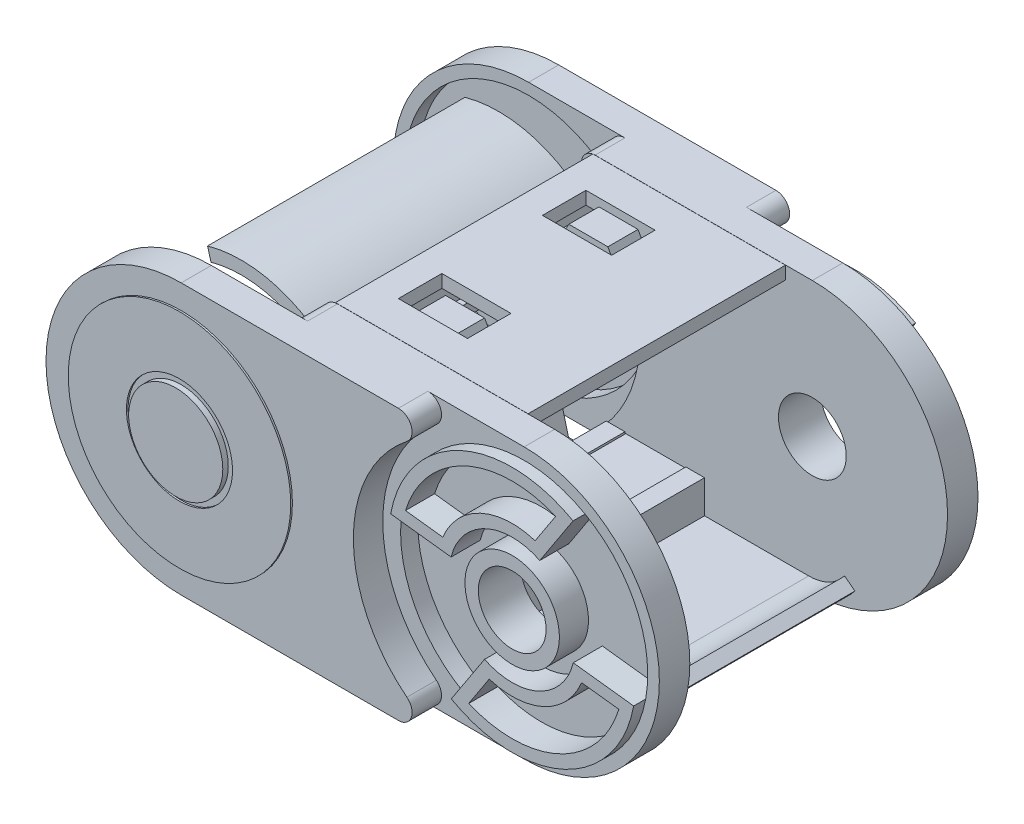
SolidWorks part; units mm, degrees
material "ABS"
ref_plane "Front Plane" through (0, 0, 0) normal (0, 0, 1) x (1, 0, 0)
ref_plane "Top Plane" through (0, 0, 0) normal (0, 1, 0) x (1, 0, 0)
ref_plane "Right Plane" through (0, 0, 0) normal (1, 0, 0) x (0, 0, -1)
sketch "Sketch1" plane through (0, 0, 0) normal (0, 0, 1) x (1, 0, 0)
  line L0 (0, 19.75) -> (45.8, 19.75)
  line L2 (45.8, -19.75) -> (0, -19.75)
  line L3 (0, 0) -> (45.8, 0) construction
  line L4 (22.9, 0) -> (22.9, 19.75) construction
  arc A0 (0, 19.75) -> (0, -19.75) centre (0, 0) ccw
  arc A1 (45.8, 19.75) -> (45.8, -19.75) centre (45.8, 0) cw
  point P1 (-19.75, 0)
  point P12 (65.55, 0)
  dimension "D1" = 39.5
  dimension "D2" = 85.3
  dimension "D3" = 45.8
extrude "Boss-Extrude1" add sketch "Sketch1" against normal blind 8.75 from offset 27.575
sketch "Sketch3" plane through (0, 0, 27.575) normal (0, 0, 1) x (1, 0, 0)
  line L6 (65.55, 0) -> (25.15, 0) construction
  circle A2 centre (45.8, 0) radius 20.65
  circle A3 centre (0, 0) radius 16.25
  arc A4 (45.8, -19.75) -> (45.8, 19.75) centre (45.8, 0) ccw construction
  circle A5 centre (0, 0) radius 7.75
  circle A6 centre (0, 0) radius 5.15
  point P4 (65.55, 0)
  dimension "D1" = 40.4
  dimension "D2" = 10.3
  dimension "D3" = 15.5
  dimension "D4" = 32.5
extrude "Cut-Extrude2" cut sketch "Sketch3" against normal blind 4.3 contours A2
extrude "Cut-Extrude10" cut sketch "Sketch3<3>" against normal through all contours A6 region at (0, 0, 27.575)
sketch "Sketch3<3>" plane through (0, 0, 27.575) normal (0, 0, 1) x (1, 0, 0) same geometry as "Sketch3"
extrude "Boss-Extrude11" add sketch "Sketch3<4>" along normal blind 0.25 contours A3 A5 region at (-15.7904, 0, 27.575)
sketch "Sketch3<4>" plane through (0, 0, 27.575) normal (0, 0, 1) x (1, 0, 0) same geometry as "Sketch3"
sketch "Sketch8" plane through (0, 0, 18.825) normal (0, 0, -1) x (-1, 0, 0)
  line L0 (19.75, 0) -> (-20.65, 0) construction
  circle A0 centre (0, 0) radius 20.65
  arc A1 (0, -19.75) -> (0, 19.75) centre (0, 0) ccw construction
  point P3 (-20.65, 0)
  point P4 (19.75, 0)
  dimension "D1" = 40.4
extrude "Cut-Extrude6" cut sketch "Sketch8" against normal blind 4.35
sketch "Sketch9" plane through (0, 0, 23.175) normal (0, 0, -1) x (-1, 0, 0)
  circle A0 centre (0, 0) radius 18.1
  dimension "D1" = 36.2
extrude "Cut-Extrude7" cut sketch "Sketch9" against normal blind 6.5 from surface starting at face at (34.5075, 0, 18.825)
sketch "Sketch10" plane through (0, 0, 25.325) normal (0, 0, -1) x (-1, 0, 0)
  line L0 (0, 0) -> (16.75, 0) construction
  line L1 (8.5625, 2.5) -> (16.75, 3.2)
  line L2 (16.75, 3.2) -> (16.75, -3.2)
  line L3 (16.75, -3.2) -> (8.5625, -2.5)
  line L4 (8.8724, 0.9207) -> (15.15, 1.4574)
  line L5 (15.15, 1.4574) -> (15.15, -1.4574)
  line L6 (15.15, -1.4574) -> (8.8724, -0.9207)
  line L7 (8.6988, 0.9058) -> (15.15, 1.4574) construction
  line L8 (15.15, -1.4574) -> (8.6988, -0.9058) construction
  line L9 (0, 0) -> (0, -8.92) construction
  line L10 (-8.8724, 0.9207) -> (-15.15, 1.4574)
  line L11 (-15.15, 1.4574) -> (-15.15, -1.4574)
  line L12 (-15.15, -1.4574) -> (-8.8724, -0.9207)
  line L13 (-16.75, -3.2) -> (-8.5625, -2.5)
  line L14 (-16.75, 3.2) -> (-16.75, -3.2)
  line L15 (-8.5625, 2.5) -> (-16.75, 3.2)
  circle A0 centre (0, 0) radius 7
  arc A1 (-8.8724, 0.9207) -> (-8.8724, -0.9207) centre (0, 0) ccw
  arc A2 (-8.5625, -2.5) -> (8.5625, -2.5) centre (0, 0) ccw
  arc A3 (8.5625, 2.5) -> (-8.5625, 2.5) centre (0, 0) ccw
  arc A4 (8.8724, -0.9207) -> (8.8724, 0.9207) centre (0, 0) ccw
  point P7 (16.75, 0)
  dimension "D1" = 14
  dimension "D2" = 17.84
  dimension "D3" = 5
  dimension "D4" = 6.4
  dimension "D5" = 16.75
  dimension "D6" = 1.6
extrude "Boss-Extrude3" add sketch "Sketch10" along normal blind 3.9
fillet "Fillet1" radius 0.5 4 edges at (-16.75, -3.2, 23.375) (-16.75, 3.2, 23.375) (16.75, -3.2, 23.375) (16.75, 3.2, 23.375)
sketch "Sketch11" plane through (0, 0, 21.425) normal (0, 0, -1) x (-1, 0, 0)
  circle A0 centre (0, 0) radius 7 construction
  circle A1 centre (0, 0) radius 7
extrude "Cut-Extrude8" cut sketch "Sketch11" against normal blind 4.6
fillet "Fillet2" radius 2 4 edges at (6.0299, 19.75, 21) (6.0299, -19.75, 21) (39.7701, -19.75, 25.425) (39.7701, 19.75, 25.425)
sketch "Sketch20" plane through (0, 0, 23.275) normal (0, 0, 1) x (1, 0, 0)
  circle A1 centre (45.8, 0) radius 18.05
  circle A2 centre (45.8, 0) radius 4.95
  dimension "D1" = 36.1
  dimension "D2" = 9.9
extrude "Cut-Extrude11" cut sketch "Sketch20" against normal through all contours A2 region at (45.8, 0, 23.275)
extrude "Cut-Extrude12" cut sketch "Sketch20<3>" against normal offset from surface (2.5 mm away) 6.8 contours A1 up to face at (16.25, 0, 27.575)
sketch "Sketch20<3>" plane through (0, 0, 23.275) normal (0, 0, 1) x (1, 0, 0) same geometry as "Sketch20"
sketch "Sketch21" plane through (0, 0, 20.775) normal (0, 0, 1) x (1, 0, 0)
  line L0 (54.6961, 15.7055) -> (49.8334, 8.2687)
  line L1 (45.8, 0) -> (38.1717, 16.3589) construction
  line L2 (28.0506, 3.2805) -> (36.8732, 2.2253)
  line L3 (45.8, 0) -> (63.6996, 8.3467) construction
  line L4 (45.8, 0) -> (0, 0) construction
  line L5 (52.1515, 15.0116) -> (49.152, 10.4243)
  line L6 (30.2178, 4.7838) -> (35.6599, 4.1329)
  line L7 (36.9039, -15.7055) -> (41.7666, -8.2687)
  line L8 (39.4485, -15.0116) -> (42.448, -10.4243)
  line L9 (61.3822, -4.7838) -> (55.9401, -4.1329)
  line L10 (63.5494, -3.2805) -> (54.7268, -2.2253)
  circle A0 centre (45.8, 0) radius 4.95 construction
  circle A1 centre (45.8, 0) radius 4.95
  circle A2 centre (45.8, 0) radius 6.9
  arc A3 (49.8334, 8.2687) -> (36.8732, 2.2253) centre (45.8, 0) ccw
  circle A4 centre (45.8, 0) radius 18.05 construction
  arc A5 (54.6961, 15.7055) -> (28.0506, 3.2805) centre (45.8, 0) ccw
  arc A6 (45.8, -19.75) -> (45.8, 19.75) centre (45.8, 0) ccw construction
  arc A7 (0, 19.75) -> (0, -19.75) centre (0, 0) ccw construction
  arc A8 (49.152, 10.4243) -> (35.6599, 4.1329) centre (45.8, 0) ccw
  arc A9 (52.1515, 15.0116) -> (30.2178, 4.7838) centre (45.8, 0) ccw
  arc A10 (54.7268, -2.2253) -> (41.7666, -8.2687) centre (45.8, 0) cw
  arc A11 (55.9401, -4.1329) -> (42.448, -10.4243) centre (45.8, 0) cw
  arc A12 (61.3822, -4.7838) -> (39.4485, -15.0116) centre (45.8, 0) cw
  arc A13 (63.5494, -3.2805) -> (36.9039, -15.7055) centre (45.8, 0) cw
  point P19 (-19.75, 0)
  dimension "D1" = 13.8
  dimension "D2" = 29.4
  dimension "D4" = 18.4
  dimension "D3" = 14.3
  dimension "D5" = 25
  dimension "D6" = 1.75
extrude "Boss-Extrude12" add sketch "Sketch21" along normal blind 4.25
sketch "Sketch12" plane through (0, 0, 18.825) normal (0, 0, -1) x (-1, 0, 0)
  line L0 (-27.45, 17.15) -> (-18.35, 17.15)
  line L1 (-22.9, 17.15) -> (-22.9, 13.25) construction
  line L2 (-27.45, 17.15) -> (-28.275, 15.65)
  line L3 (-28.275, 14.85) -> (-27.25, 14.85)
  line L4 (-27.25, 14.85) -> (-27.25, 13.25)
  line L5 (-18.55, 14.85) -> (-18.55, 13.25)
  line L6 (-17.525, 14.85) -> (-18.55, 14.85)
  line L7 (-18.35, 17.15) -> (-17.525, 15.65)
  line L8 (-18.55, 13.25) -> (-27.25, 13.25)
  line L9 (-28.275, 15.65) -> (-28.275, 14.85)
  line L10 (0, 0) -> (-45.8, 0) construction
  line L20 (-17.525, 15.65) -> (-17.525, 14.85)
  line L21 (-22.9, -17.15) -> (-22.9, -13.25) construction
  line L22 (-17.525, -15.65) -> (-17.525, -14.85)
  line L23 (-28.275, -15.65) -> (-28.275, -14.85)
  line L24 (-18.55, -13.25) -> (-27.25, -13.25)
  line L25 (-18.35, -17.15) -> (-17.525, -15.65)
  line L26 (-17.525, -14.85) -> (-18.55, -14.85)
  line L27 (-18.55, -14.85) -> (-18.55, -13.25)
  line L28 (-27.25, -14.85) -> (-27.25, -13.25)
  line L29 (-28.275, -14.85) -> (-27.25, -14.85)
  line L30 (-27.45, -17.15) -> (-28.275, -15.65)
  line L31 (-27.45, -17.15) -> (-18.35, -17.15)
  point P3 (-22.9, 17.15)
  point P17 (-22.9, 0)
  dimension "D1" = 10.75
  dimension "D3" = 26.5
  dimension "D4" = 34.3
  dimension "D5" = 8.7
  dimension "D6" = 2.3
  dimension "D7" = 0.8
  dimension "D8" = 9.1
extrude "Boss-Extrude4" add sketch "Sketch12" along normal blind 10.92
sketch "Sketch13" plane through (0, 0, 7.905) normal (0, 0, -1) x (-1, 0, 0)
  line L0 (-26.725, 17.15) -> (-25.75, 18.9)
  line L1 (-18.35, 17.15) -> (-27.45, 17.15) construction
  line L2 (-25.75, 18.9) -> (-20.05, 18.9)
  line L3 (-20.05, 18.9) -> (-19.075, 17.15)
  line L4 (-26.725, 17.15) -> (-19.075, 17.15)
  line L5 (-22.9, 18.9) -> (-22.9, 17.15) construction
  line L6 (0, 0) -> (-45.8, 0) construction
  line L8 (-20.05, -18.9) -> (-19.075, -17.15)
  line L9 (-26.725, -17.15) -> (-19.075, -17.15)
  line L10 (-26.725, -17.15) -> (-25.75, -18.9)
  line L11 (-25.75, -18.9) -> (-20.05, -18.9)
  point P8 (-22.9, 17.15)
  dimension "D1" = 7.65
  dimension "D2" = 5.7
  dimension "D3" = 1.75
extrude "Boss-Extrude5" add sketch "Sketch13" against normal blind 4.4 from offset 1.1 offset against normal yes
sketch "Sketch14" plane through (0, 0, 0) normal (0, 0, 1) x (1, 0, 0)
  line L0 (45.2873, 19.75) -> (8.74, 19.75)
  line L1 (45.8, 19.75) -> (14.0698, 19.75) construction
  line L2 (8.74, 19.75) -> (7.2253, 13.8823)
  line L3 (52.05, 16.3994) -> (50.5543, 15.2605)
  line L4 (45.2873, 17.87) -> (30.075, 17.87)
  line L5 (10.1963, 17.87) -> (8.4, 10.9111)
  line L6 (-10.34, 11.7476) -> (-9.0979, 10.3364)
  line L8 (30.075, 13.05) -> (30.075, 17.87)
  line L9 (27.35, 13.05) -> (30.075, 13.05)
  line L10 (27.35, 13.05) -> (27.35, 14.75)
  line L11 (27.35, 14.75) -> (28.375, 14.75)
  line L12 (28.375, 14.75) -> (28.375, 17.87)
  line L13 (28.375, 17.87) -> (17.425, 17.87)
  line L14 (41.15, 17.87) -> (10.1963, 17.87) construction
  line L15 (18.45, 13.05) -> (15.725, 13.05)
  line L16 (15.725, 13.05) -> (15.725, 17.87)
  line L17 (22.9, 13.25) -> (22.9, 19.75) construction
  line L18 (18.45, 13.25) -> (18.45, 14.75)
  line L19 (17.425, 14.75) -> (17.425, 15.65)
  line L20 (18.45, 14.75) -> (17.425, 14.75)
  line L21 (18.45, 13.05) -> (18.45, 14.75)
  line L22 (17.425, 14.75) -> (17.425, 17.87)
  line L23 (18.45, 14.75) -> (17.425, 14.75)
  line L24 (18.55, 13.25) -> (27.25, 13.25) construction
  line L25 (15.725, 17.87) -> (10.1963, 17.87)
  line L26 (52.05, 16.3994) -> (52.8335, 18.4552) construction
  line L27 (41.15, 19.75) -> (8.74, 19.75) construction
  arc A0 (7.2253, 13.8823) -> (-10.34, 11.7476) centre (0, 0) ccw
  arc A1 (8.4, 10.9111) -> (-9.0979, 10.3364) centre (0, 0) ccw
  arc A3 (45.8, -19.75) -> (45.8, 19.75) centre (45.8, 0) ccw construction
  arc A4 (52.05, 16.3994) -> (45.2873, 19.75) centre (45.2873, 11.25) ccw
  arc A5 (50.5543, 15.2605) -> (45.2873, 17.87) centre (45.2873, 11.25) ccw
  point P28 (65.55, 0)
  point P30 (45.8, 0)
  point P37 (52.05, 16.3994)
  dimension "D1" = 15.65
  dimension "D5" = 2.2
  dimension "D10" = 17
  dimension "D2" = 14.16
  dimension "D3" = 33.24
  dimension "D4" = 14.5
  dimension "D7" = 0.1
  dimension "D9" = 13.5
  dimension "D6" = 1.88
  dimension "D8" = 1.7
extrude "Boss-Extrude6" add sketch "Sketch14" along normal mid plane 37.6 separate body
sketch "Sketch15" plane through (0, 19.75, 0) normal (0, 1, 0) x (1, 0, 0)
  line L1 (27.95, -7.35) -> (17.85, -7.35)
  line L2 (27.95, -7.35) -> (27.95, -13.7)
  line L5 (27.95, -13.7) -> (17.85, -13.7)
  line L6 (17.85, -7.35) -> (17.85, -13.7)
  line L7 (22.9, -13.7) -> (22.9, -7.35) construction
  line L8 (27.95, -10.525) -> (17.85, -10.525) construction
  line L9 (0, 0) -> (44.1536, 0) construction
  line L10 (17.85, 7.35) -> (17.85, 13.7)
  line L11 (27.95, 13.7) -> (17.85, 13.7)
  line L12 (27.95, 7.35) -> (27.95, 13.7)
  line L13 (27.95, 7.35) -> (17.85, 7.35)
  line L14 (19.075, -9.005) -> (26.725, -13.405) construction
  point P14 (22.9, -11.205)
  point P172 (22.9, -10.525)
  dimension "D1" = 10.1
  dimension "D2" = 14.7
  dimension "D3" = 27.4
extrude "Cut-Extrude9" cut sketch "Sketch15" against normal up to surface (5 mm away) up to face at (27.8625, 14.75, 0)
sketch "Sketch16" plane through (0, 13.05, 0) normal (0, -1, 0) x (1, 0, 0)
  line L5 (30.075, 0) -> (15.725, 0) construction
  line L6 (30.075, 18.8) -> (30.075, -18.8) construction
  line L13 (15.725, 18.8) -> (15.725, -18.8) construction
  line L14 (30.075, 1) -> (15.725, 1)
  line L15 (30.075, -1) -> (15.725, -1)
  line L16 (30.075, 1) -> (30.075, -1)
  line L17 (15.725, 1) -> (15.725, -1)
  dimension "D1" = 1
  dimension "D2" = 1
extrude "Boss-Extrude7" add sketch "Sketch16" against normal up to surface (4.82 mm away) up to face at (37.6812, 17.87, 0)
sketch "Sketch18" plane through (0, 0, 27.575) normal (0, 0, 1) x (1, 0, 0)
  circle A0 centre (0, 0) radius 6.875
  dimension "D1" = 13.75
extrude "Boss-Extrude9" add sketch "Sketch18" along normal blind 0.8 separate body
sketch "Sketch19" plane through (0, 0, 27.575) normal (0, 0, -1) x (-1, 0, 0)
  circle A2 centre (0, 0) radius 5.1
  circle A4 centre (0, 0) radius 5.1
  dimension "D1" = 0.05
extrude "Boss-Extrude10" add sketch "Sketch19" along normal blind 8
mirror "Mirror1" about plane through (0, 0, 0) normal (0, 0, 1) of bodies 113 121
mirror "Mirror2" about plane through (0, 0, 0) normal (0, 1, 0) of bodies 118 115
sketch "Sketch22" plane through (0, -19.75, 0) normal (0, -1, 0) x (1, 0, 0)
  line L0 (45.8, 18.825) -> (65.55, 18.825) construction
  line L1 (54.05, 18.825) -> (41.9, 18.825)
  line L2 (54.05, 18.825) -> (54.05, -18.825)
  line L3 (54.05, -18.825) -> (41.9, -18.825)
  line L4 (41.9, 18.825) -> (41.9, -18.825)
  line L5 (47.975, -18.825) -> (47.975, 18.825) construction
  line L6 (54.05, 0) -> (41.9, 0) construction
  line L7 (14.0698, -18.825) -> (45.8, -18.825) construction
  line L8 (52.05, 18.8) -> (52.05, -18.8) construction
  line L9 (25.75, 13.405) -> (20.05, 13.405) construction
  point P14 (22.9, 13.405)
  point P268 (47.975, 0)
  dimension "D1" = 2
  dimension "D2" = 19
extrude "Cut-Extrude13" cut sketch "Sketch22" against normal through all
sketch "Sketch23" plane through (0, 0, 0) normal (0, 0, 1) x (1, 0, 0)
  line L0 (15.225, 17.87) -> (14.1999, 13.8987)
  line L1 (8.4, 10.9111) -> (10.1963, 17.87) construction
  line L2 (10.1963, 17.87) -> (15.725, 17.87) construction
  line L3 (15.225, 17.87) -> (15.225, 19.75)
  line L4 (41.9, 19.75) -> (8.74, 19.75) construction
  line L5 (15.225, 19.75) -> (13.7687, 19.75)
  line L6 (13.7687, 19.75) -> (12.3795, 14.3685)
  line L7 (10.1963, 17.87) -> (8.376, 18.3399) construction
  line L8 (8.74, 19.75) -> (7.2253, 13.8823) construction
  line L9 (14.7124, 15.8843) -> (12.8921, 16.3542) construction
  line L10 (-4.925, 17.5729) -> (-4.4177, 15.7627)
  line L11 (30.075, 13.05) -> (30.075, 17.87) construction
  arc A1 (10.3855, 12.6538) -> (-4.4177, 15.7627) centre (0, 0) ccw
  arc A3 (11.5782, 14.107) -> (-4.925, 17.5729) centre (0, 0) ccw
  arc A4 (12.3795, 14.3685) -> (11.5782, 14.107) centre (11.8954, 14.4935) cw
  arc A5 (14.1999, 13.8987) -> (10.3855, 12.6538) centre (11.8954, 14.4935) cw
  dimension "D3" = 0.5
  dimension "D5" = 2.38
  dimension "D6" = 18.25
  dimension "D1" = 0.5
  dimension "D2" = 35
  dimension "D4" = 1.88
sketch "Sketch24" plane through (0, 0, 0) normal (0, 0, 1) x (1, 0, 0)
  line L1 (15.225, 19.75) -> (-22.9807, 19.75)
  line L2 (15.225, 19.75) -> (15.225, 7.5314)
  line L3 (15.225, 7.5314) -> (-22.9807, 7.5314)
  line L4 (-22.9807, 19.75) -> (-22.9807, 7.5314)
  line L5 (-3.8779, 7.5314) -> (-3.8779, 19.75) construction
  line L6 (15.225, 13.6407) -> (-22.9807, 13.6407) construction
  point P108 (-3.8779, 13.6407)
extrude "Cut-Extrude14" cut sketch "Sketch24" against normal through all both and the other way through all
extrude "Boss-Extrude13" add sketch "Sketch23" along normal up to surface (18.8 mm away) and the other way up to surface (18.8 mm away) up to face at (24.3156, 16.12, 18.8) other way up to face at (24.3156, 16.12, -18.8)
